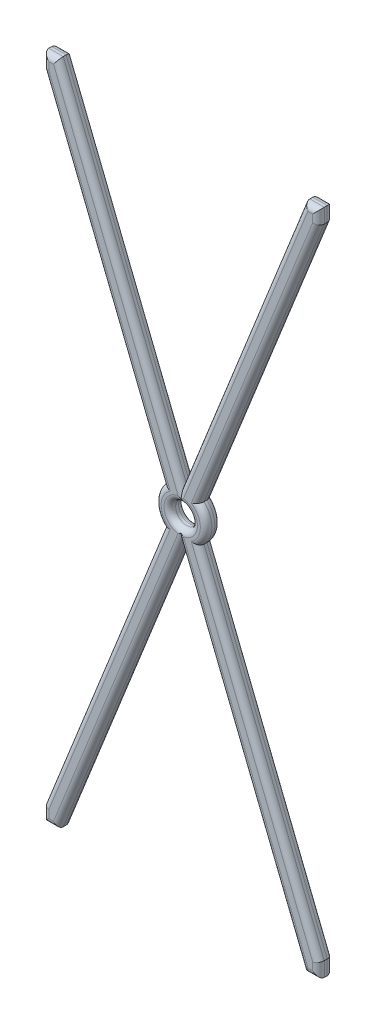
SolidWorks part; units mm, degrees
ref_plane "Ebene vorne" through (0, 0, 0) normal (0, 0, 1) x (1, 0, 0)
ref_plane "Ebene oben" through (0, 0, 0) normal (0, 1, 0) x (1, 0, 0)
ref_plane "Ebene rechts" through (0, 0, 0) normal (1, 0, 0) x (0, 0, -1)
sketch "Skizze1" plane through (0, 0, 0) normal (0, 0, 1) x (1, 0, 0)
  line L0 (0, 2300) -> (50, 2300)
  line L1 (0, 0) -> (50, 0)
  line L2 (0, 0) -> (0, 50)
  line L5 (50, 2300) -> (475, 1237.5)
  line L6 (950, 50) -> (950, 0)
  line L7 (900, 0) -> (475, 1062.5)
  line L8 (0, 2250) -> (0, 2300)
  line L9 (950, 2300) -> (900, 2300)
  line L10 (900, 2300) -> (475, 1237.5)
  line L12 (50, 0) -> (475, 1062.5)
  line L13 (950, 2250) -> (950, 2300)
  line L14 (440, 1150) -> (0, 50)
  line L15 (510, 1150) -> (950, 50)
  line L18 (900, 0) -> (950, 0)
  line L19 (440, 1150) -> (0, 2250)
  line L20 (510, 1150) -> (950, 2250)
  dimension "D1" = 950
  dimension "D2" = 2300
  dimension "D3" = 50
  dimension "D4" = 50
  dimension "D5" = 50
  dimension "D6" = 50
  dimension "D7" = 50
  dimension "D8" = 50
  dimension "D9" = 50
  dimension "D10" = 50
extrude "Aufsatz-Linear austragen1" add sketch "Skizze1" along normal blind 50
sketch "Skizze2" plane through (0, 0, 50) normal (0, 0, 1) x (1, 0, 0)
  circle A0 centre (475, 1150) radius 35
  circle A1 centre (475, 1150) radius 87.5
extrude "Aufsatz-Linear austragen2" add sketch "Skizze2" against normal blind 50
sketch "Skizze4" plane through (0, 0, 50) normal (0, 0, 1) x (1, 0, 0)
  line L0 (475, 1237.5) -> (475, 1062.5)
  circle A0 centre (475, 1150) radius 37.5
  dimension "D1" = 75
extrude "Schnitt-Linear austragen1" cut sketch "Skizze4" against normal blind 50 contours L0 A0 | L0 A0 region at (490.9155, 1150, 50) region at (459.0845, 1150, 50)
fillet "Verrundung1" radius 20 19 edges at (25, 0, 50) (0, 25, 50) (207.3276, 568.319, 50) (387.5, 1150, 50) (207.3276, 1731.681, 50) (0, 2275, 50) (25, 2300, 50) (262.5, 1768.75, 50) (687.5, 1768.75, 50) (925, 2300, 50) (950, 2275, 50) (742.6724, 1731.681, 50) (562.5, 1150, 50) (742.6724, 568.319, 50) (950, 25, 50) (925, 0, 50) (687.5, 531.25, 50) (262.5, 531.25, 50) (512.5, 1150, 50)
fillet "Verrundung2" radius 20 19 edges at (0, 25, 0) (25, 0, 0) (262.5, 531.25, 0) (687.5, 531.25, 0) (925, 0, 0) (950, 25, 0) (742.6724, 568.319, 0) (562.5, 1150, 0) (742.6724, 1731.681, 0) (950, 2275, 0) (925, 2300, 0) (687.5, 1768.75, 0) (262.5, 1768.75, 0) (25, 2300, 0) (0, 2275, 0) (207.3276, 1731.681, 0) (387.5, 1150, 0) (207.3276, 568.319, 0) (512.5, 1150, 0)
